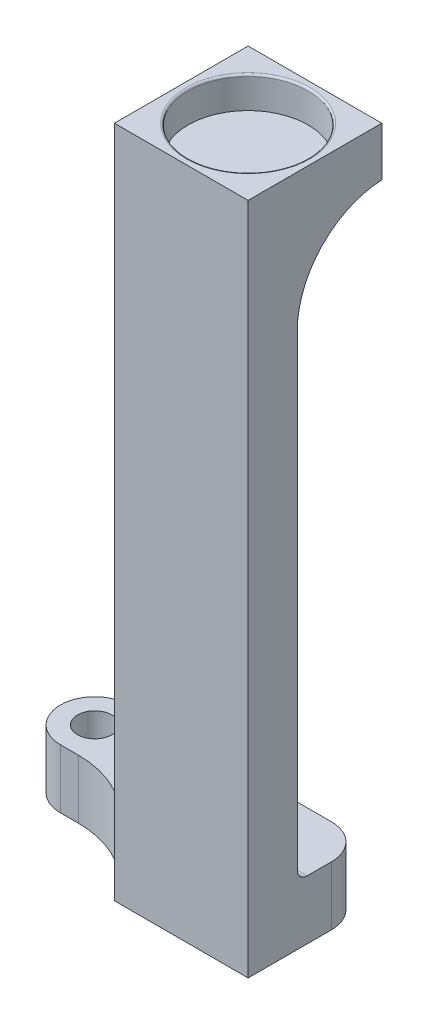
SolidWorks part; units mm, degrees
ref_plane "Front Plane" through (0, 0, 0) normal (0, 0, 1) x (1, 0, 0)
ref_plane "Top Plane" through (0, 0, 0) normal (0, 1, 0) x (1, 0, 0)
ref_plane "Right Plane" through (0, 0, 0) normal (1, 0, 0) x (0, 0, -1)
sketch "Sketch1" plane through (0, 0, 0) normal (0, 1, 0) x (1, 0, 0)
  line L1 (-6.8, 6.8) -> (6.8, 6.8)
  line L2 (-6.8, 6.8) -> (-6.8, -6.8)
  line L3 (-6.8, -6.8) -> (6.8, -6.8)
  line L4 (6.8, 6.8) -> (6.8, -6.8)
  line L5 (-6.8, 6.8) -> (6.8, -6.8) construction
  line L6 (-6.8, -6.8) -> (6.8, 6.8) construction
  point P0 (0, 0)
  dimension "D1" = 13.6
  dimension "D2" = 13.6
extrude "Boss-Extrude1" add sketch "Sketch1" along normal blind 5
sketch "Sketch2" plane through (0, 5, 0) normal (0, 1, 0) x (1, 0, 0)
  circle A0 centre (0, 0) radius 6.1
  dimension "D1" = 12.2
extrude "Cut-Extrude1" cut sketch "Sketch2" against normal blind 3.2
sketch "Sketch3" plane through (0, 0, 0) normal (0, -1, 0) x (1, 0, 0)
  line L0 (6.8, 6.8) -> (6.8, -6.8) construction
  line L1 (-6.8, 6.8) -> (6.8, 6.8)
  line L2 (-6.8, 6.8) -> (-6.8, 1.8)
  line L3 (-6.8, 1.8) -> (6.8, 1.8)
  line L4 (6.8, 6.8) -> (6.8, 1.8)
  dimension "D1" = 5
extrude "Boss-Extrude2" add sketch "Sketch3" along normal blind 63.5
sketch "Sketch4" plane through (0, 1.8, 0) normal (0, 1, 0) x (1, 0, 0)
  point P0 (0, 0)
fillet "Fillet1" radius 0.2 1 edges at (0, 5, 6.1)
fillet "Fillet2" radius 9 1 edges at (0, 0, 1.8)
sketch "Sketch10" plane through (0, 0, 1.8) normal (0, 0, -1) x (-1, 0, 0)
  line L1 (-6.8, -63.5) -> (20.8, -63.5)
  line L2 (-6.8, -63.5) -> (-6.8, -57.5)
  line L3 (-6.8, -57.5) -> (20.8, -57.5)
  line L4 (20.8, -63.5) -> (20.8, -57.5)
  dimension "D1" = 6
  dimension "D2" = 27.6
extrude "Boss-Extrude5" add sketch "Sketch10" along normal blind 7
sketch "Sketch11" plane through (0, -57.5, 0) normal (0, 1, 0) x (1, 0, 0)
  line L0 (-6.8, -1.8) -> (-6.8, 5.2) construction
  line L1 (-20.8, 5.2) -> (6.8, 5.2) construction
  line L2 (-6.8, 1.7) -> (-10.3, 1.7) construction
  line L3 (-10.3, 1.7) -> (-13.8, 1.7) construction
  line L4 (-17.3, 1.7) -> (-20.8, 1.7) construction
  line L5 (-20.8, 5.2) -> (-20.8, -1.8) construction
  line L6 (-13.8, 1.7) -> (-17.3, 1.7) construction
  circle A0 centre (-10.3, 1.7) radius 1.75
  circle A1 centre (-17.3, 1.7) radius 1.75
  dimension "D1" = 3.5
  dimension "D2" = 3.5
extrude "Cut-Extrude4" cut sketch "Sketch11" against normal through all
sketch "Sketch12" plane through (0, -57.5, 0) normal (0, 1, 0) x (1, 0, 0)
  line L0 (-10.3, 3.45) -> (-10.3, -0.05)
  circle A0 centre (-10.3, 1.7) radius 1.75
  point P4 (-10.3, 1.7)
  point P6 (0, 0)
fillet "Fillet3" radius 10 1 edges at (-6.8, -60.5, 1.8)
fillet "Fillet4" radius 3.5 3 edges at (-20.8, -60.5, 1.8) (-20.8, -60.5, -5.2) (6.8, -60.5, -5.2)
fillet "Fillet5" radius 1 2 edges at (-6.8, -57.5, 4.3) (0, -57.5, 1.8)
mirror "Mirror1" [suppressed] of bodies 109
delete or keep bodies "Body-Delete/Keep 1" [suppressed] type delete bodies bodies 109
